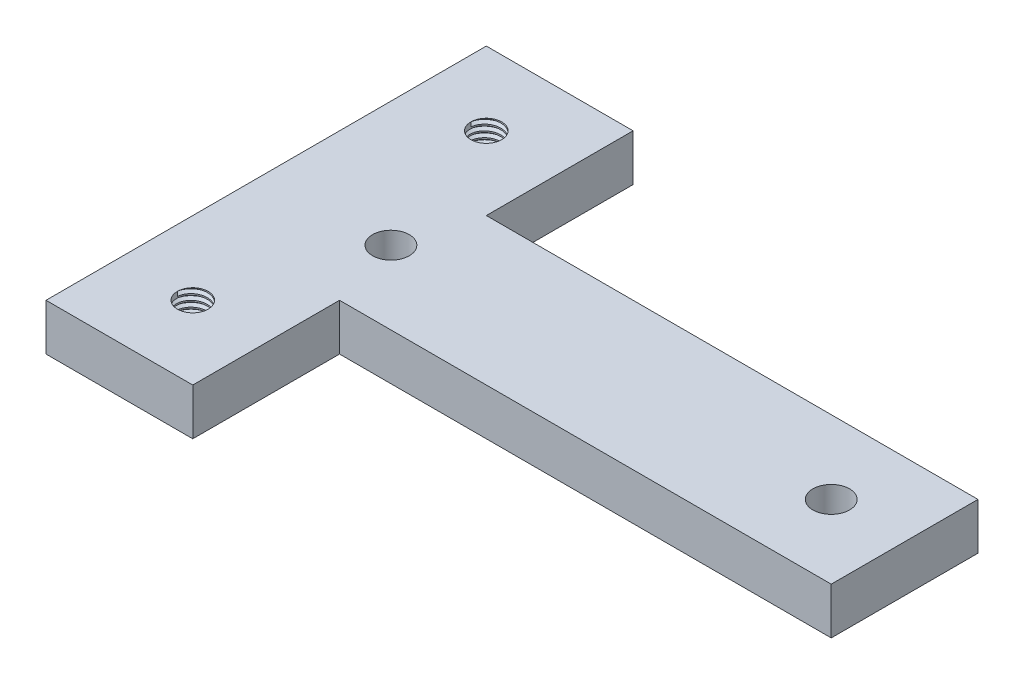
SolidWorks part; units mm, degrees
ref_plane "Front Plane" through (0, 0, 0) normal (0, 0, 1) x (1, 0, 0)
ref_plane "Top Plane" through (0, 0, 0) normal (0, 1, 0) x (1, 0, 0)
ref_plane "Right Plane" through (0, 0, 0) normal (1, 0, 0) x (0, 0, -1)
sketch "Sketch1" plane through (0, 0, 0) normal (0, 1, 0) x (1, 0, 0)
  line L0 (-30, 0) -> (30, 0) construction
  line L1 (-37, -20) -> (-37, 20) construction
  line L3 (-47, 0) -> (-47, 30)
  line L4 (-47, 30) -> (-27, 30)
  line L5 (-27, 30) -> (-27, 10)
  line L6 (-27, 10) -> (40, 10)
  line L7 (40, 10) -> (40, -10)
  line L8 (40, -10) -> (-27, -10)
  line L9 (-27, -10) -> (-27, -30)
  line L10 (-27, -30) -> (-47, -30)
  line L11 (-47, -30) -> (-47, 0)
  circle A0 centre (-30, 0) radius 2.5
  circle A1 centre (30, 0) radius 2.5
  circle A2 centre (-37, 20) radius 2.1
  circle A3 centre (-37, -20) radius 2.1
  point P4 (0, 0)
  point P10 (-37, 0)
  dimension "D2" = 5
  dimension "D3" = 5
  dimension "D5" = 4.2
  dimension "D6" = 4.2
  dimension "D1" = 60
  dimension "D4" = 40
  dimension "D7" = 37
  dimension "D9" = 10
  dimension "D10" = 10
  dimension "D11" = 10
  dimension "D12" = 10
  dimension "D13" = 10
  dimension "D14" = 10
  dimension "D15" = 10
extrude "Boss-Extrude1" add sketch "Sketch1" along normal blind 3.175 and the other way blind 3.175
thread "Thread1" pitch 0.8 method cut profile "Thread Profile1" start angle 0, offset 0, length 10, pitch 0.8, diameter 4.2
ref_plane "Plane1" through (-39.1, 3.175, -20) normal (0, 0, 1) x (-1, 0, 0)
sketch "Thread Profile1" plane through (-39.1, 3.175, -20) normal (0, 0, 1) x (-1, 0, 0)
  line L0 (0, 0) -> (0, 0.8) construction
  line L1 (0, 0) -> (0.433, 0.25)
  line L2 (0.433, 0.25) -> (0.433, 0.35)
  line L3 (0.433, 0.35) -> (0, 0.6)
  line L4 (0.433, 0.3) -> (0, 0.3) construction
  line L11 (0, 0) -> (0, 0.6)
  point P2 (0, 0)
  dimension "Pitch" = 0.8
  dimension "Profile_Angle" = 60
  dimension "Profile_Land" = 0.1
  dimension "Profile_Height" = 0.433
thread "Thread2" pitch 0.8 method cut profile "Thread Profile2" start angle 0, offset 0, length 10, pitch 0.8, diameter 4.2
ref_plane "Plane2" through (-39.1, 3.175, 20) normal (0, 0, 1) x (-1, 0, 0)
sketch "Thread Profile2" plane through (-39.1, 3.175, 20) normal (0, 0, 1) x (-1, 0, 0)
  line L0 (0, 0) -> (0, 0.8) construction
  line L1 (0, 0) -> (0.433, 0.25)
  line L2 (0.433, 0.25) -> (0.433, 0.35)
  line L3 (0.433, 0.35) -> (0, 0.6)
  line L4 (0.433, 0.3) -> (0, 0.3) construction
  line L11 (0, 0) -> (0, 0.6)
  point P2 (0, 0)
  dimension "Pitch" = 0.8
  dimension "Profile_Angle" = 60
  dimension "Profile_Land" = 0.1
  dimension "Profile_Height" = 0.433
